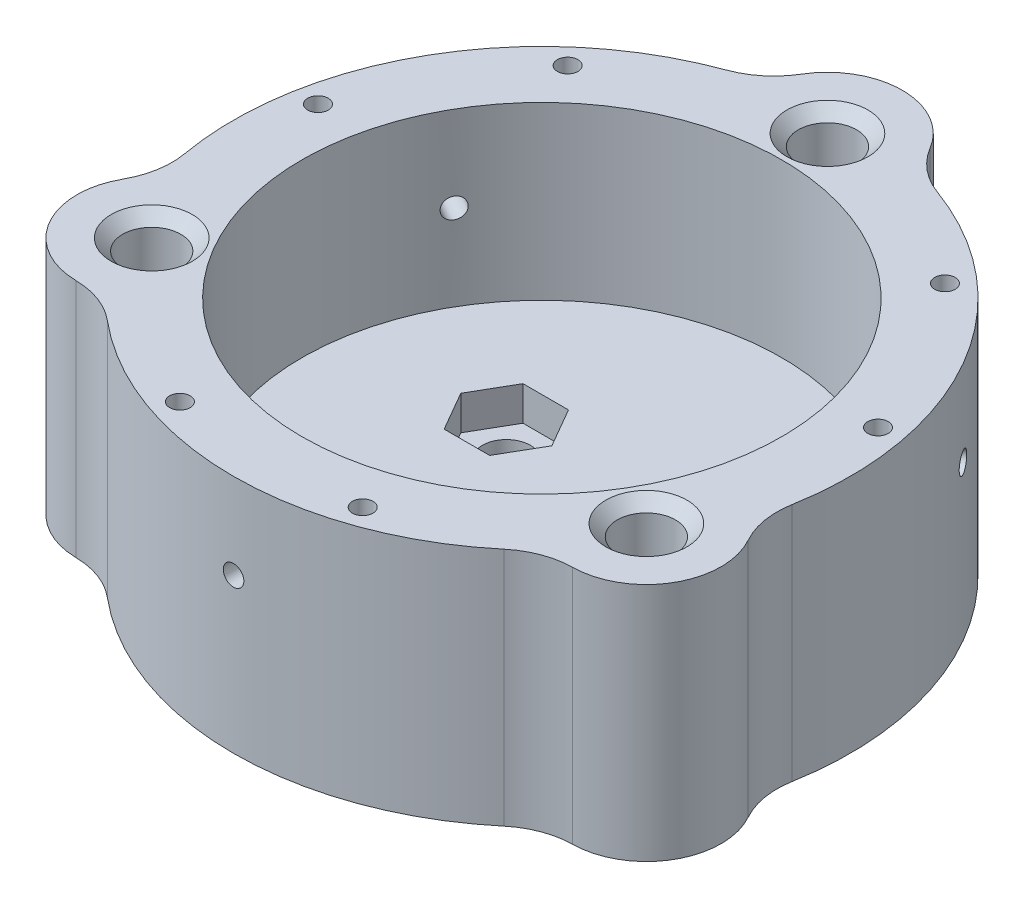
SolidWorks part; units mm, degrees
ref_plane "Спереди" through (0, 0, 0) normal (0, 0, 1) x (1, 0, 0)
ref_plane "Сверху" through (0, 0, 0) normal (0, 1, 0) x (1, 0, 0)
ref_plane "Справа" through (0, 0, 0) normal (1, 0, 0) x (0, 0, -1)
sketch "Эскиз1" plane through (0, 0, 0) normal (0, 1, 0) x (1, 0, 0)
  circle A0 centre (0, 0) radius 25 construction
  circle A1 centre (0, 25) radius 2.55
  circle A3 centre (0, 25) radius 6.55
  circle A4 centre (0, 0) radius 21
  circle A5 centre (0, 0) radius 27
  circle A6 centre (21.6506, -12.5) radius 6.55
  circle A7 centre (21.6506, -12.5) radius 2.55
  circle A8 centre (-21.6506, -12.5) radius 6.55
  circle A9 centre (-21.6506, -12.5) radius 2.55
  dimension "D1" = 50
  dimension "D2" = 5.1
  dimension "D3" = 4
  dimension "D5" = 4
  dimension "D4" = 2
  dimension "D6" = 3
extrude "Бобышка-Вытянуть1" add sketch "Эскиз1" along normal blind 15 contours A5 A3 A1 | A3 A5 A1 A4 | A6 A5 A3 A4 | A8 A4 A3 A5 | A7 A5 A6 A4 | A7 A5 A6 | A8 A5 A6 A4 | A9 A5 A8 | A9 A5 A8 A4 region at (2.4448, 0, -26.1369) region at (0, 0, -28.7811) region at (18.7721, 0, -10.8381) region at (-18.7721, 0, -10.8381) region at (-23.1355, 0, 6.2905) region at (-24.9251, 0, 14.3905) region at (24.9251, 0, 14.3905) region at (24.991, 0, 9.7744) region at (0, 0, 21.6761)
sketch "Эскиз2" plane through (0, 0, 0) normal (0, -1, 0) x (1, 0, 0)
  arc A27 (25.9264, 7.5381) -> (19.4914, 18.6839) centre (21.6506, 12.5) ccw
  arc A28 (6.435, -26.2219) -> (25.9264, 7.5381) centre (0, 0) ccw
  arc A29 (-6.435, -26.2219) -> (6.435, -26.2219) centre (0, -25) ccw
  arc A30 (-25.9264, 7.5381) -> (-6.435, -26.2219) centre (0, 0) ccw
  arc A31 (-19.4914, 18.6839) -> (-25.9264, 7.5381) centre (-21.6506, 12.5) ccw
  arc A32 (19.4914, 18.6839) -> (-19.4914, 18.6839) centre (0, 0) ccw
  arc A33 (25.9264, 7.5381) -> (19.4914, 18.6839) centre (21.6506, 12.5) ccw
  arc A34 (6.435, -26.2219) -> (25.9264, 7.5381) centre (0, 0) ccw
  arc A35 (-6.435, -26.2219) -> (6.435, -26.2219) centre (0, -25) ccw
  arc A36 (-25.9264, 7.5381) -> (-6.435, -26.2219) centre (0, 0) ccw
  arc A37 (-19.4914, 18.6839) -> (-25.9264, 7.5381) centre (-21.6506, 12.5) ccw
  arc A38 (19.4914, 18.6839) -> (-19.4914, 18.6839) centre (0, 0) ccw
  dimension "D1" = 0
extrude "Бобышка-Вытянуть2" add sketch "Эскиз2" along normal blind 6
fillet "Скругление1" radius 7 6 edges at (6.435, 4.5, -26.2219) (-6.435, 4.5, -26.2219) (-25.9264, 4.5, 7.5381) (-19.4914, 4.5, 18.6839) (19.4914, 4.5, 18.6839) (25.9264, 4.5, 7.5381)
chamfer "Фаска1" distance 1 angle 45 3 edges at (0, 15, -22.45) (21.6506, 15, 15.05) (-21.6506, 15, 15.05)
sketch "Эскиз4" plane through (0, -6, 0) normal (0, -1, 0) x (1, 0, 0)
  circle A0 centre (0, 0) radius 8.5 construction
  circle A1 centre (0, 8.5) radius 2.1
  circle A2 centre (7.3612, -4.25) radius 2.1
  circle A3 centre (-7.3612, -4.25) radius 2.1
  dimension "D1" = 17
  dimension "D2" = 4.2
  dimension "D3" = 3
extrude "Вырез-Вытянуть1" cut sketch "Эскиз4" against normal through all
sketch "Эскиз5" plane through (0, 0, 0) normal (0, 1, 0) x (1, 0, 0)
  line L0 (1.9919, -11.95) -> (3.9837, -8.5)
  line L1 (5.3694, 0.8) -> (9.3531, 0.8)
  line L2 (9.3531, 0.8) -> (11.3449, 4.25)
  line L3 (11.3449, 4.25) -> (9.3531, 7.7)
  line L4 (9.3531, 7.7) -> (5.3694, 7.7)
  line L5 (5.3694, 7.7) -> (3.3775, 4.25)
  line L6 (3.3775, 4.25) -> (5.3694, 0.8)
  line L7 (3.9837, -8.5) -> (1.9919, -5.05)
  line L8 (1.9919, -5.05) -> (-1.9919, -5.05)
  line L9 (-1.9919, -5.05) -> (-3.9837, -8.5)
  line L10 (-3.9837, -8.5) -> (-1.9919, -11.95)
  line L11 (-1.9919, -11.95) -> (1.9919, -11.95)
  line L12 (-11.3449, 4.25) -> (-9.3531, 0.8)
  line L13 (-9.3531, 0.8) -> (-5.3694, 0.8)
  line L14 (-5.3694, 0.8) -> (-3.3775, 4.25)
  line L15 (-3.3775, 4.25) -> (-5.3694, 7.7)
  line L16 (-5.3694, 7.7) -> (-9.3531, 7.7)
  line L17 (-9.3531, 7.7) -> (-11.3449, 4.25)
  circle A2 centre (7.3612, 4.25) radius 3.45 construction
  circle A3 centre (0, -8.5) radius 3.45 construction
  circle A4 centre (-7.3612, 4.25) radius 3.45 construction
  circle A5 centre (0, -8.5) radius 2.1 construction
  dimension "D1" = 6.9
  dimension "D2" = 3
extrude "Вырез-Вытянуть2" cut sketch "Эскиз5" against normal blind 3
sketch "Эскиз6" plane through (0, 15, 0) normal (0, 1, 0) x (1, 0, 0)
  line L0 (0, 0) -> (0, -25) construction
  line L1 (-8, -23.6854) -> (8, -23.6854) construction
  circle A0 centre (0, 0) radius 25 construction
  circle A1 centre (-8, -23.6854) radius 0.9
  circle A2 centre (8, -23.6854) radius 0.9
  circle A3 centre (-16.5122, 18.7709) radius 0.9
  circle A4 centre (-24.5122, 4.9145) radius 0.9
  circle A5 centre (24.5122, 4.9145) radius 0.9
  circle A6 centre (16.5122, 18.7709) radius 0.9
  dimension "D2" = 1.8
  dimension "D3" = 1.8
  dimension "D1" = 16
  dimension "D4" = 3
extrude "Вырез-Вытянуть3" cut sketch "Эскиз6" against normal through all
sketch "Эскиз7" plane through (0, 0, 0) normal (0, 0, 1) x (1, 0, 0)
  line L0 (17.3524, 15) -> (-17.3524, 15) construction
  line L1 (0, 15) -> (0, 0) construction
  circle A0 centre (0, 7.5) radius 0.9
  dimension "D1" = 1.8
extrude "Вырез-Вытянуть4" cut sketch "Эскиз7" along normal through all
pattern_circular "Круговой массив1" count 3 over 360 about axis through (0, 15, 0) along (0, -1, 0) of "Вырез-Вытянуть4"
equation "\"motor_diameter\"= 30"
equation "\"mm_diameter\"= IIF ( \"motor_diameter\" < 34 , 41 , \"motor_diameter\" + 8 )"
equation "\"upper_shafts_diameter\"= 5"
equation "\"upper_shats_length\"= 180"
equation "\"upper_bearing_d1\"= 10"
equation "\"upper_bearing_d2\"= 5"
equation "\"upper_bearing_h\"= 15"
equation "\"lower_shafts_diameter\"= 5"
equation "\"lower_shafts_length\"= 180"
equation "\"lower_bearing_d1\"= 10"
equation "\"lower_bearing_d2\"= 5"
equation "\"lower_bearing_h\"= 15"
equation "\"print_offset\"= 0.2"
equation "\"bh_screws_d\"= 2"
equation "\"bh_screws_h\"= 20"
equation "\"bh_screws_hh_d\"= 3.4"
equation "\"bh_screws_hh_h\"= 2"
equation "\"bh_nut_d\"= 3.8"
equation "\"bh_nut_h\"= 2"
equation "\"motor_screws_d\"= 3"
equation "\"motor_screws_h\"= 16"
equation "\"motor_screws_hh_d\"= 5.5"
equation "\"motor_screws_hh_h\"= 3"
equation "\"plate_hole_distance\"= 25.4"
equation "\"plate_screws_d\"= 6.5"
equation "\"shafts_diameter\"= IIF ( \"mm_diameter\" < 42 , 42 + 8 , \"mm_diameter\" + 8 )"
equation "\"central_hole_diameter\"= 8"
equation "\"bh_thikness\"= 4"
equation "\"D1@Эскиз1\"=\"shafts_diameter\""
equation "\"D2@Эскиз1\" = \"upper_shafts_diameter\" + \"print_offset\" / 2"
equation "\"D3@Эскиз1\"=\"bh_thikness\""
equation "\"D1@Бобышка-Вытянуть1\"= \"upper_bearing_h\""
equation "\"D1@Бобышка-Вытянуть2\"=6"
equation "\"D4@Эскиз1\"=\"D3@Эскиз1\"/2"
equation "\"D2@Эскиз4\"=\"ends_screws_d\"+\"print_offset\""
equation "\"D1@Эскиз5\"=\"ends_nut_d\"+\"print_offset\"/2"
equation "\"D1@Вырез-Вытянуть2\"=\"ends_nut_h\""
equation "\"D5@Эскиз1\"=\"bh_thikness\""
equation "\"ends_screws_d\"= 4"
equation "\"ends_screws_h\"= 16"
equation "\"ends_screws_hh_d\"= 6.7"
equation "\"ends_screws_hh_h\"= 4.1"
equation "\"ends_nut_d\"= 6.8"
equation "\"ends_nut_h\"= 3"
equation "\"D2@Эскиз6\"=\"bh_screws_d\"-\"print_offset\""
equation "\"D3@Эскиз6\"=\"D2@Эскиз6\""
equation "\"D1@Эскиз7\"=\"bh_screws_d\"-\"print_offset\""
